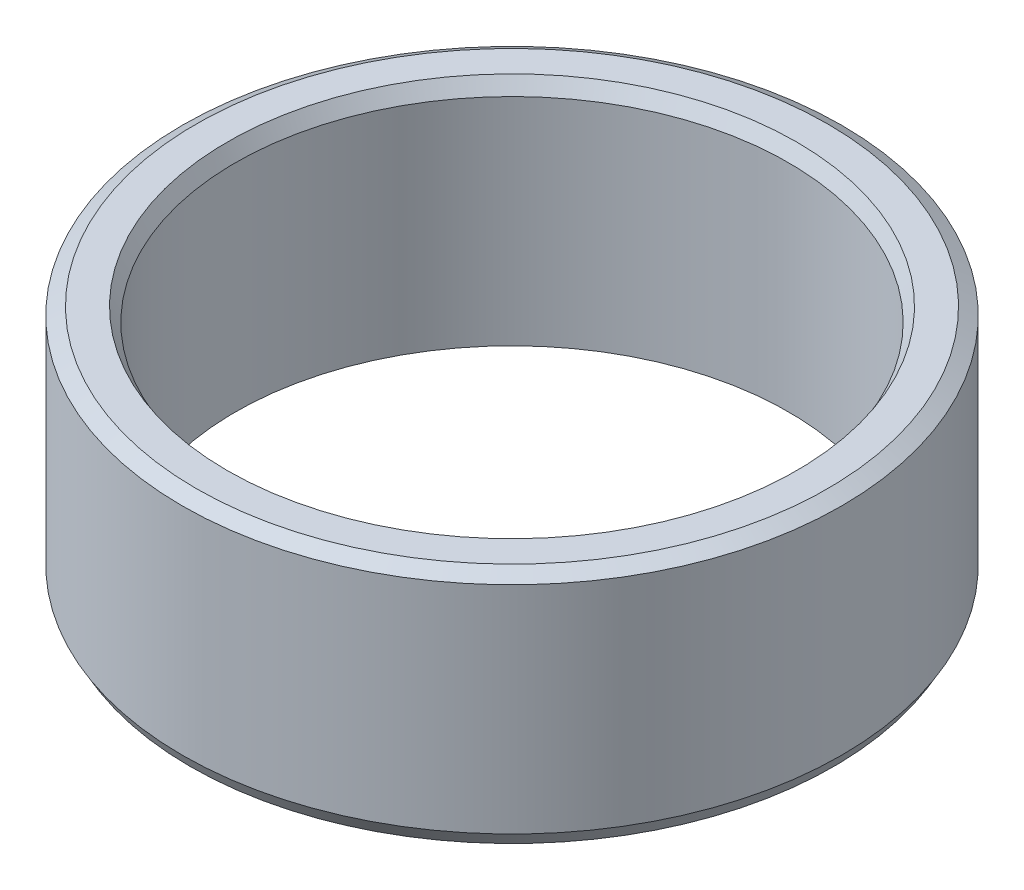
SolidWorks part; units mm, degrees
ref_plane "Front Plane" through (0, 0, 0) normal (0, 0, 1) x (1, 0, 0)
ref_plane "Top Plane" through (0, 0, 0) normal (0, 1, 0) x (1, 0, 0)
ref_plane "Right Plane" through (0, 0, 0) normal (1, 0, 0) x (0, 0, -1)
sketch "Sketch1" plane through (0, 0, 0) normal (0, 1, 0) x (1, 0, 0)
  circle A0 centre (0, 0) radius 50
  dimension "SLEEVE_OD" = 100
extrude "Boss-Extrude1" add sketch "Sketch1" along normal blind 36.0682
sketch "Sketch2" plane through (0, 0, 0) normal (0, 1, 0) x (1, 0, 0)
  circle A0 centre (0, 0) radius 41.9476
  dimension "BORE_D" = 83.8953
extrude "Cut-Extrude1" cut sketch "Sketch2" along normal through all
chamfer "Chamfer1" distance 1.2188 angle 60 4 edges at (0, 36.0682, 41.9476) (0, 0, 41.9476) (0, 0, 50) (0, 36.0682, 50) first distance on face at (0, 36.0682, 41.9476) first distance on face at (0, 0, 41.9476) first distance on face at (0, 36.0682, 50)
